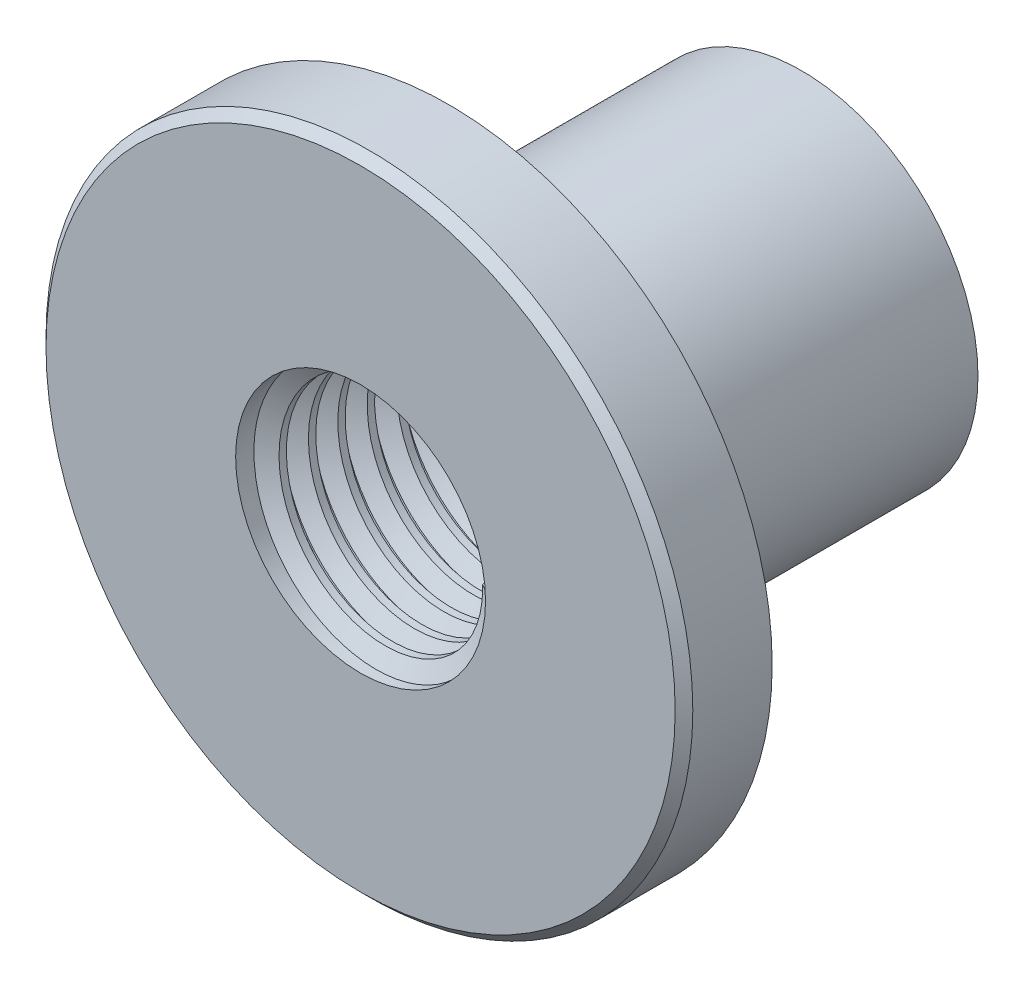
SolidWorks part; units mm, degrees
material "1060 Alloy"
ref_plane "Front Plane" through (0, 0, 0) normal (0, 0, 1) x (1, 0, 0)
ref_plane "Top Plane" through (0, 0, 0) normal (0, 1, 0) x (1, 0, 0)
ref_plane "Right Plane" through (0, 0, 0) normal (1, 0, 0) x (0, 0, -1)
sketch "Sketch1" plane through (0, 0, 0) normal (1, 0, 0) x (0, 0, -1)
  line L1 (0, 0) -> (3, 0)
  line L2 (0, 0) -> (0, -11)
  line L3 (0, -11) -> (3, -11)
  line L4 (3, 0) -> (3, -11)
  line L5 (3, -11) -> (15, -11)
  line L6 (3, -11) -> (3, -5)
  line L7 (3, -5) -> (15, -5)
  line L8 (15, -11) -> (15, -5)
  dimension "D1" = 11
  dimension "D2" = 3
  dimension "D3" = 6
  dimension "D4" = 12
revolve "Revolve4" add sketch "Sketch1" angle 360 about L5 region at (0, -5.5, -1.5) region at (0, -8, -9)
chamfer "Chamfer1" distance 0.3 angle 45 1 edges at (11, -11, 0)
sketch "Sketch6" plane through (0, 0, -15) normal (0, 0, -1) x (-1, 0, 0)
  circle A0 centre (0, -11) radius 6 construction
  point P0 (0, -11)
  point P1 (0, 0)
hole_wizard "M10 Tapped Hole1" positions "3DSketch2" profile "Sketch7" tap size "M10" standard "DIN"
sketch3d "3DSketch2"
  point P0 (0, -11, -15)
sketch "Sketch7" plane through (0, -11, -15) normal (1, 0, 0) x (0, 1, 0)
  line L0 (0, 0) -> (0, 27.0537)
  line L1 (0, 27.0537) -> (4.25, 24.5)
  line L2 (4.25, 24.5) -> (4.25, 0)
  line L5 (4.25, 0) -> (0, 0)
  line L10 (0, 27.0537) -> (-4.25, 24.5) construction
  line L11 (0, -6.35) -> (0, 107.95) construction
  dimension "Tap Drill Dia." = 8.5
  dimension "Tap Drill Depth" = 24.5
  dimension "Drill Angle" = 118
cosmetic thread "Hole Thread1" parameters "D1"=15, "D2"=10
thread "Thread3" pitch 1 method extrude profile "Thread Profile5" start angle 0, offset 0, length 0, pitch 1, diameter 8.5
ref_plane "Plane5" through (4.25, -11, -15) normal (0, -1, 0) x (1, 0, 0)
sketch "Thread Profile5" plane through (4.25, -11, -15) normal (0, -1, 0) x (1, 0, 0)
  line L0 (0, 0) -> (0, 1) construction
  line L11 (0, 0) -> (0, 0.875)
  line L12 (0, 0.875) -> (-0.5413, 0.5625)
  line L13 (-0.5413, 0.5625) -> (-0.5413, 0.3125)
  line L15 (-0.5413, 0.3125) -> (0, 0)
  line L17 (-0.5413, 0.4375) -> (0, 0.4375) construction
  point P2 (0, 0)
  dimension "Pitch" = 1
  dimension "Profile_Angle" = 60
  dimension "Profile_Land" = 0.25
  dimension "Profile_Height" = 0.5413
